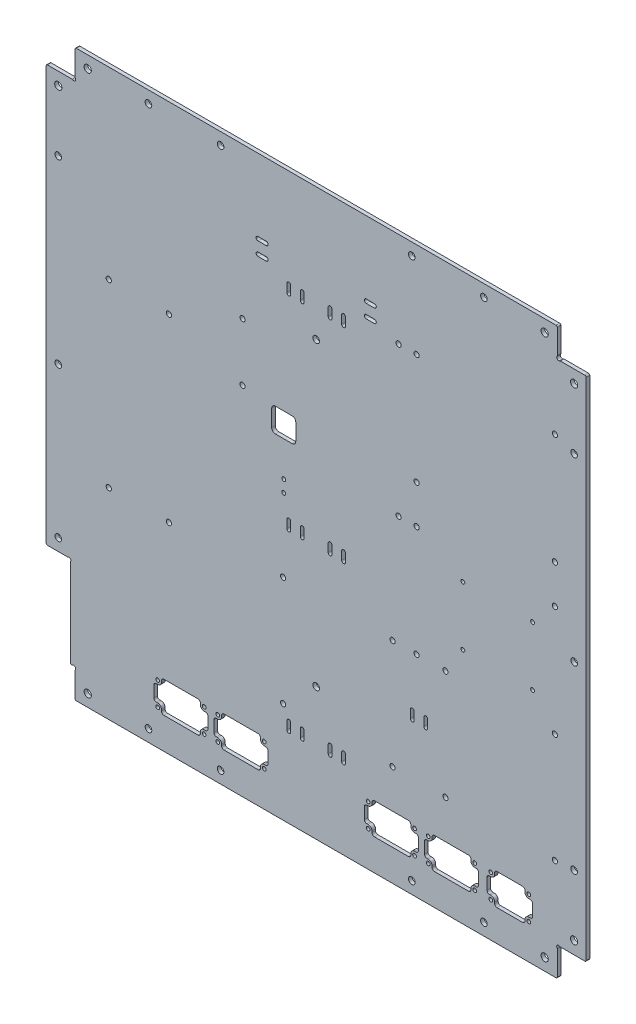
SolidWorks part; units mm, degrees
material "Acrylic (Medium-high impact)"
ref_plane "Front" through (0, 0, 0) normal (0, 0, 1) x (1, 0, 0)
ref_plane "Top" through (0, 0, 0) normal (0, 1, 0) x (1, 0, 0)
ref_plane "Right" through (0, 0, 0) normal (1, 0, 0) x (0, 0, -1)
sketch "Sketch2" plane through (0, 0, 0) normal (0, 0, 1) x (1, 0, 0)
  line L1 (0, 0) -> (449, 0)
  line L2 (0, 0) -> (0, 470)
  line L3 (0, 470) -> (449, 470)
  line L4 (449, 0) -> (449, 470)
  dimension "D1" = 449
  dimension "D2" = 470
extrude "Boss-Extrude1" add sketch "Sketch2" along normal blind 3
sketch "Sketch23" plane through (0, 0, 0) normal (0, 0, -1) x (-1, 0, 0)
  line L0 (-449, 470) -> (0, 470) construction
  line L1 (-449, 470) -> (-429, 470)
  line L2 (-449, 470) -> (-449, 450)
  line L3 (-449, 450) -> (-429, 450)
  line L4 (-429, 470) -> (-429, 450)
  line L5 (0, 470) -> (-20, 470)
  line L6 (0, 470) -> (0, 450)
  line L7 (0, 450) -> (-20, 450)
  line L8 (-20, 470) -> (-20, 450)
  line L9 (0, 470) -> (0, 0) construction
  line L11 (0, 0) -> (-20, 0)
  line L12 (0, 0) -> (0, 20)
  line L13 (0, 20) -> (-20, 20)
  line L14 (-20, 0) -> (-20, 20)
  line L15 (-449, 0) -> (-429, 0)
  line L16 (-449, 0) -> (-449, 20)
  line L17 (-449, 20) -> (-429, 20)
  line L18 (-429, 0) -> (-429, 20)
  dimension "D1" = 20
  dimension "D2" = 20
hole_wizard "M5 Clearance Hole1" positions "Sketch4" profile "Sketch5" hole size "M5" standard "ANSI Metric" end condition up to next
sketch "Sketch4" plane through (0, 0, 0) normal (0, 0, -1) x (-1, 0, 0)
  line L0 (-224.5, 470) -> (-224.5, 0) construction
  line L1 (-449, 470) -> (0, 470) construction
  line L2 (0, 0) -> (-449, 0) construction
  line L3 (-429, 460) -> (-364, 460) construction
  line L6 (-364, 460) -> (-85, 460) construction
  line L7 (-85, 460) -> (-20, 460) construction
  line L9 (-449, 235) -> (0, 235) construction
  line L10 (-449, 0) -> (-449, 470) construction
  line L12 (0, 470) -> (0, 0) construction
  line L13 (-439, 450) -> (-439, 20) construction
  line L18 (-10, 450) -> (-10, 20) construction
  line L21 (-429, 10) -> (-20, 10) construction
  line L31 (-20, 470) -> (-20, 450) construction
  line L32 (-429, 470) -> (-429, 450) construction
  line L33 (-449, 450) -> (-429, 450) construction
  line L34 (-449, 20) -> (-429, 20) construction
  line L35 (-429, 0) -> (-429, 20) construction
  line L36 (0, 450) -> (-20, 450) construction
  line L37 (0, 20) -> (-20, 20) construction
  line L38 (-20, 0) -> (-20, 20) construction
  point P13 (-224.5, 360)
  point P17 (-224.5, 110)
  point P24 (-364, 460)
  point P29 (-85, 460)
  point P54 (-304, 460)
  point P56 (-145, 460)
  point P59 (-85, 10)
  point P60 (-145, 10)
  point P61 (-304, 10)
  point P62 (-364, 10)
  point P83 (-439, 385)
  point P85 (-439, 85)
  point P92 (-10, 110)
  point P93 (-10, 385)
  point P97 (-439, 235)
  point P103 (-10, 235)
  dimension "D5" = 65
  dimension "D8" = 65
  dimension "D3" = 100
  dimension "D2" = 100
  dimension "D1" = 60
  dimension "D4" = 60
  dimension "D6" = 90
  dimension "D9" = 65
sketch "Sketch5" plane through (10, 235, 0) normal (1, 0, 0) x (0, 1, 0)
  line L0 (0, 0) -> (0, 3)
  line L1 (0, 3) -> (2.75, 3)
  line L2 (2.75, 3) -> (2.75, 0)
  line L5 (2.75, 0) -> (0, 0)
  line L11 (0, -6.35) -> (0, 107.95) construction
  dimension "Thru Hole Dia." = 5.5
  dimension "Thru Hole Depth" = 3
sketch "Sketch10" plane through (0, 0, 0) normal (0, 0, -1) x (-1, 0, 0)
  line L0 (-20, 20) -> (-429, 20) construction
  line L1 (-134.5, 26) -> (-89.5, 26) construction
  line L2 (-134.5, 26) -> (-134.5, 52) construction
  line L3 (-134.5, 52) -> (-89.5, 52) construction
  line L4 (-89.5, 26) -> (-89.5, 52) construction
  line L7 (-224.5, 20) -> (-224.5, 145.1565) construction
  line L8 (-128.15, 52) -> (-128.15, 45.65)
  line L15 (-139.5, 52) -> (-184.5, 52) construction
  line L16 (-139.5, 52) -> (-139.5, 26) construction
  line L17 (-139.5, 26) -> (-184.5, 26) construction
  line L18 (-184.5, 52) -> (-184.5, 26) construction
  line L22 (-128.15, 45.65) -> (-134.5, 45.65)
  line L23 (-134.5, 45.65) -> (-134.5, 32.35)
  line L24 (-134.5, 32.35) -> (-128.15, 32.35)
  line L25 (-128.15, 32.35) -> (-128.15, 26)
  line L26 (-128.15, 26) -> (-95.85, 26)
  line L27 (-95.85, 26) -> (-95.85, 32.35)
  line L28 (-95.85, 32.35) -> (-89.5, 32.35)
  line L29 (-89.5, 32.35) -> (-89.5, 45.65)
  line L30 (-89.5, 45.65) -> (-95.85, 45.65)
  line L31 (-95.85, 45.65) -> (-95.85, 52)
  line L32 (-95.85, 52) -> (-128.15, 52)
  line L33 (-178.15, 52) -> (-178.15, 45.65)
  line L34 (-178.15, 45.65) -> (-184.5, 45.65)
  line L35 (-184.5, 45.65) -> (-184.5, 32.35)
  line L36 (-184.5, 32.35) -> (-178.15, 32.35)
  line L37 (-178.15, 32.35) -> (-178.15, 26)
  line L38 (-178.15, 26) -> (-145.85, 26)
  line L39 (-145.85, 26) -> (-145.85, 32.35)
  line L40 (-145.85, 32.35) -> (-139.5, 32.35)
  line L41 (-139.5, 32.35) -> (-139.5, 45.65)
  line L42 (-139.5, 45.65) -> (-145.85, 45.65)
  line L43 (-145.85, 45.65) -> (-145.85, 52)
  line L44 (-145.85, 52) -> (-178.15, 52)
  line L45 (-264.5, 52) -> (-264.5, 26) construction
  line L46 (-309.5, 26) -> (-264.5, 26) construction
  line L47 (-309.5, 52) -> (-309.5, 26) construction
  line L48 (-309.5, 52) -> (-264.5, 52) construction
  line L49 (-359.5, 26) -> (-359.5, 52) construction
  line L50 (-314.5, 52) -> (-359.5, 52) construction
  line L51 (-314.5, 26) -> (-314.5, 52) construction
  line L52 (-314.5, 26) -> (-359.5, 26) construction
  line L53 (-303.15, 52) -> (-270.85, 52)
  line L54 (-303.15, 45.65) -> (-303.15, 52)
  line L55 (-309.5, 45.65) -> (-303.15, 45.65)
  line L56 (-309.5, 32.35) -> (-309.5, 45.65)
  line L57 (-303.15, 32.35) -> (-309.5, 32.35)
  line L58 (-303.15, 26) -> (-303.15, 32.35)
  line L59 (-270.85, 26) -> (-303.15, 26)
  line L60 (-270.85, 32.35) -> (-270.85, 26)
  line L61 (-264.5, 32.35) -> (-270.85, 32.35)
  line L62 (-264.5, 45.65) -> (-264.5, 32.35)
  line L63 (-270.85, 45.65) -> (-264.5, 45.65)
  line L64 (-270.85, 52) -> (-270.85, 45.65)
  line L65 (-353.15, 52) -> (-320.85, 52)
  line L66 (-353.15, 45.65) -> (-353.15, 52)
  line L67 (-359.5, 45.65) -> (-353.15, 45.65)
  line L68 (-359.5, 32.35) -> (-359.5, 45.65)
  line L69 (-353.15, 32.35) -> (-359.5, 32.35)
  line L70 (-353.15, 26) -> (-353.15, 32.35)
  line L71 (-320.85, 26) -> (-353.15, 26)
  line L72 (-320.85, 32.35) -> (-320.85, 26)
  line L73 (-314.5, 32.35) -> (-320.85, 32.35)
  line L74 (-314.5, 45.65) -> (-314.5, 32.35)
  line L75 (-320.85, 45.65) -> (-314.5, 45.65)
  line L76 (-320.85, 52) -> (-320.85, 45.65)
  line L77 (0, 0) -> (-449, 0) construction
  dimension "D1" = 6.35
  dimension "D2" = 45
  dimension "D3" = 40
  dimension "D4" = 26
  dimension "D5" = 5
  dimension "D6" = 26
extrude "extruder panel cutouts" cut sketch "Sketch10" against normal through all
sketch "Sketch16" plane through (0, 0, 0) normal (0, 0, -1) x (-1, 0, 0)
  line L0 (-353.15, 26) -> (-320.85, 26) construction
  line L1 (-366.5, 26) -> (-404.5, 26) construction
  line L2 (-366.5, 26) -> (-366.5, 52) construction
  line L3 (-366.5, 52) -> (-404.5, 52) construction
  line L4 (-404.5, 26) -> (-404.5, 52) construction
  line L6 (-398.15, 52) -> (-398.15, 45.65)
  line L7 (-398.15, 45.65) -> (-404.5, 45.65)
  line L8 (-404.5, 45.65) -> (-404.5, 32.35)
  line L9 (-404.5, 32.35) -> (-398.15, 32.35)
  line L10 (-398.15, 32.35) -> (-398.15, 26)
  line L11 (-398.15, 26) -> (-372.85, 26)
  line L12 (-372.85, 26) -> (-372.85, 32.35)
  line L13 (-372.85, 32.35) -> (-366.5, 32.35)
  line L14 (-366.5, 32.35) -> (-366.5, 45.65)
  line L15 (-366.5, 45.65) -> (-372.85, 45.65)
  line L16 (-372.85, 45.65) -> (-372.85, 52)
  line L17 (-372.85, 52) -> (-398.15, 52)
  line L18 (-449, 0) -> (-449, 470) construction
  dimension "D1" = 26
  dimension "D2" = 38
  dimension "D3" = 44.5
  dimension "D4" = 6.35
extrude "z_motor_panel_cutout" cut sketch "Sketch16" against normal blind 10
fillet "Fillet1" radius 3.175 20 edges at (95.85, 45.65, 1.5) (95.85, 32.35, 1.5) (128.15, 32.35, 1.5) (128.15, 45.65, 1.5) (178.15, 32.35, 1.5) (178.15, 45.65, 1.5) (145.85, 32.35, 1.5) (145.85, 45.65, 1.5) (353.15, 45.65, 1.5) (353.15, 32.35, 1.5) (320.85, 32.35, 1.5) (320.85, 45.65, 1.5) (303.15, 32.35, 1.5) (303.15, 45.65, 1.5) (270.85, 32.35, 1.5) (270.85, 45.65, 1.5) (398.15, 32.35, 1.5) (372.85, 45.65, 1.5) (372.85, 32.35, 1.5) (398.15, 45.65, 1.5)
sketch "Sketch17" plane through (0, 0, 0) normal (0, 0, -1) x (-1, 0, 0)
  circle A0 centre (-401.325, 48.825) radius 1.55
  circle A1 centre (-369.675, 48.825) radius 1.55
  circle A2 centre (-369.675, 29.175) radius 1.55
  circle A3 centre (-401.325, 29.175) radius 1.55
  circle A4 centre (-356.325, 48.825) radius 1.55
  circle A5 centre (-317.675, 48.825) radius 1.55
  circle A6 centre (-317.675, 29.175) radius 1.55
  circle A7 centre (-356.325, 29.175) radius 1.55
  circle A8 centre (-306.325, 48.825) radius 1.55
  circle A9 centre (-267.675, 48.825) radius 1.55
  circle A10 centre (-267.675, 29.175) radius 1.55
  circle A11 centre (-306.325, 29.175) radius 1.55
  circle A12 centre (-181.325, 48.825) radius 1.55
  circle A13 centre (-142.675, 48.825) radius 1.55
  circle A14 centre (-142.675, 29.175) radius 1.55
  circle A15 centre (-181.325, 29.175) radius 1.55
  circle A16 centre (-131.325, 48.825) radius 1.55
  circle A17 centre (-92.675, 48.825) radius 1.55
  circle A18 centre (-92.675, 29.175) radius 1.55
  circle A19 centre (-131.325, 29.175) radius 1.55
  dimension "D1" = 3.1
extrude "Cut-Extrude3" cut sketch "Sketch17" against normal through all
sketch "Sketch7" plane through (0, 0, 0) normal (0, 0, -1) x (-1, 0, 0)
  line L0 (-449, 0) -> (-449, 470) construction
  line L1 (-423, 299) -> (-308, 299) construction
  line L2 (-423, 299) -> (-423, 391) construction
  line L3 (-423, 391) -> (-308, 391) construction
  line L4 (-308, 299) -> (-308, 391) construction
  line L5 (-423, 299) -> (-308, 391) construction
  line L6 (-423, 391) -> (-308, 299) construction
  line L7 (-304, 295) -> (-427, 295) construction
  line L8 (-304, 295) -> (-304, 395) construction
  line L9 (-304, 395) -> (-427, 395) construction
  line L10 (-427, 295) -> (-427, 395) construction
  line L11 (-304, 295) -> (-427, 395) construction
  line L12 (-304, 395) -> (-427, 295) construction
  line L14 (-423, 175) -> (-308, 175) construction
  line L15 (-423, 175) -> (-423, 267) construction
  line L16 (-423, 267) -> (-308, 267) construction
  line L17 (-308, 175) -> (-308, 267) construction
  line L18 (-423, 175) -> (-308, 267) construction
  line L19 (-423, 267) -> (-308, 175) construction
  line L20 (-304, 171) -> (-427, 171) construction
  line L21 (-304, 171) -> (-304, 271) construction
  line L22 (-304, 271) -> (-427, 271) construction
  line L23 (-427, 171) -> (-427, 271) construction
  line L24 (-304, 171) -> (-427, 271) construction
  line L25 (-304, 271) -> (-427, 171) construction
  circle A0 centre (-423, 391) radius 2.15
  circle A1 centre (-308, 391) radius 2.15
  circle A2 centre (-308, 299) radius 2.15
  circle A3 centre (-423, 299) radius 2.15
  circle A4 centre (-423, 267) radius 2.15
  circle A5 centre (-308, 267) radius 2.15
  circle A6 centre (-308, 175) radius 2.15
  circle A7 centre (-423, 175) radius 2.15
  point P0 (-365.5, 345)
  point P6 (-365.5, 345)
  point P19 (-365.5, 221)
  point P25 (-365.5, 221)
  dimension "D5" = 4.3
  dimension "D12" = 4.3
  dimension "D1" = 115
  dimension "D2" = 92
  dimension "D3" = 123
  dimension "D4" = 100
  dimension "D6" = 22
  dimension "D7" = 55
  dimension "D8" = 115
  dimension "D9" = 92
  dimension "D10" = 123
  dimension "D11" = 100
  dimension "D13" = 24
extrude "Duet2 mounting holes" cut sketch "Sketch7" against normal through all
sketch "Sketch9" plane through (0, 0, 0) normal (0, 0, -1) x (-1, 0, 0)
  line L0 (0, 470) -> (0, 0) construction
  line L1 (-102, 167) -> (-52, 167) construction
  line L2 (-102, 167) -> (-102, 317) construction
  line L3 (-102, 317) -> (-52, 317) construction
  line L4 (-52, 167) -> (-52, 317) construction
  line L5 (-102, 167) -> (-52, 317) construction
  line L6 (-102, 317) -> (-52, 167) construction
  line L8 (0, 0) -> (-449, 0) construction
  line L9 (-20, 135) -> (-134, 135) construction
  line L10 (-20, 135) -> (-20, 349) construction
  line L11 (-20, 349) -> (-134, 349) construction
  line L12 (-134, 135) -> (-134, 349) construction
  line L13 (-20, 135) -> (-134, 349) construction
  line L14 (-20, 349) -> (-134, 135) construction
  circle A0 centre (-52, 317) radius 2.2
  circle A1 centre (-102, 317) radius 2.2
  circle A2 centre (-52, 167) radius 2.2
  circle A3 centre (-102, 167) radius 2.2
  point P0 (-77, 242)
  point P11 (-77, 242)
  point P21 (-77, 317)
  dimension "D1" = 50
  dimension "D3" = 4.4
  dimension "D2" = 114
  dimension "D4" = 32
  dimension "D5" = 150
  dimension "D6" = 20
  dimension "D7" = 135
extrude "psu mounting holes" cut sketch "Sketch9" against normal through all
sketch "Sketch11" plane through (0, 0, 0) normal (0, 0, -1) x (-1, 0, 0)
  line L0 (-224.5, 0) -> (-224.5, 150.8562) construction
  line L1 (0, 0) -> (-449, 0) construction
  line L2 (-163.25, 296.4) -> (-163.25, 344.4) construction
  circle A0 centre (-163.25, 344.4) radius 2.15
  circle A1 centre (-163.25, 296.4) radius 2.15
  dimension "D1" = 48
  dimension "D2" = 4.3
  dimension "D3" = 296.4
  dimension "D4" = 61.25
extrude "ssr holes" cut sketch "Sketch11" against normal through all
sketch "Sketch18" plane through (0, 0, 0) normal (0, 0, -1) x (-1, 0, 0)
  line L0 (-423, 267) -> (-293, 267) construction
  line L1 (-423, 391) -> (-293, 391) construction
  line L2 (-428, 396) -> (-288, 396) construction
  line L3 (-423, 391) -> (-293, 391) construction
  line L4 (-423, 391) -> (-423, 267) construction
  line L5 (-423, 267) -> (-293, 267) construction
  line L6 (-293, 391) -> (-293, 267) construction
  line L7 (-288, 396) -> (-288, 262) construction
  line L8 (-428, 262) -> (-288, 262) construction
  line L9 (-428, 396) -> (-428, 262) construction
  line L10 (-404.5, 246.5) -> (-346.5, 246.5) construction
  line L11 (-428, 250) -> (-343, 250) construction
  line L12 (-428, 250) -> (-428, 194) construction
  line L13 (-428, 194) -> (-343, 194) construction
  line L14 (-343, 250) -> (-343, 194) construction
  line L15 (-346.5, 246.5) -> (-346.5, 197.5) construction
  line L16 (-346.5, 197.5) -> (-404.5, 197.5) construction
  line L17 (-404.5, 197.5) -> (-404.5, 246.5) construction
  line L18 (-423, 84) -> (-423, 175) construction
  line L19 (-427.5, 79.5) -> (-327.5, 79.5) construction
  line L20 (-427.5, 79.5) -> (-427.5, 179.5) construction
  line L21 (-427.5, 179.5) -> (-327.5, 179.5) construction
  line L22 (-327.5, 79.5) -> (-327.5, 179.5) construction
  line L23 (-423, 175) -> (-332, 175) construction
  line L24 (-332, 84) -> (-332, 175) construction
  line L25 (-423, 84) -> (-332, 84) construction
  line L26 (-192.5, 179.5) -> (-292.5, 179.5) construction
  line L27 (-197, 175) -> (-288, 175) construction
  line L28 (-197, 175) -> (-197, 84) construction
  line L29 (-197, 84) -> (-288, 84) construction
  line L30 (-288, 175) -> (-288, 84) construction
  line L31 (-292.5, 179.5) -> (-292.5, 79.5) construction
  line L32 (-192.5, 79.5) -> (-292.5, 79.5) construction
  line L33 (-192.5, 179.5) -> (-192.5, 79.5) construction
  circle A0 centre (-293, 391) radius 2.15
  circle A1 centre (-423, 391) radius 2.15 construction
  circle A2 centre (-293, 267) radius 2.15
  circle A3 centre (-404.5, 246.5) radius 1.6
  circle A4 centre (-346.5, 246.5) radius 1.6
  circle A5 centre (-346.5, 197.5) radius 1.6
  circle A6 centre (-404.5, 197.5) radius 1.6
  circle A7 centre (-332, 175) radius 2.15
  circle A8 centre (-332, 84) radius 2.15
  circle A9 centre (-423, 84) radius 2.15
  circle A10 centre (-423, 175) radius 2.15 construction
  circle A11 centre (-288, 175) radius 2.15
  circle A12 centre (-288, 84) radius 2.15
  circle A13 centre (-197, 84) radius 2.15
  circle A14 centre (-163.25, 344.4) radius 2.15 construction
  circle A15 centre (-197, 175) radius 2.15
  dimension "D2" = 4.3
  dimension "D11" = 3.2
  dimension "D1" = 130
  dimension "D3" = 124
  dimension "D5" = 85
  dimension "D6" = 56
  dimension "D8" = 3.5
  dimension "D9" = 3.5
  dimension "D10" = 58
  dimension "D12" = 12
  dimension "D7" = 3.5
  dimension "D14" = 100
  dimension "D16" = 91
  dimension "D13" = 14.5
  dimension "D17" = 91
  dimension "D19" = 35
  dimension "D4" = 5
  dimension "D15" = 4.5
  dimension "D18" = 4.5
extrude "Duet3, Expanders, and Raspi Holes" cut sketch "Sketch18" against normal through all
sketch "Sketch12" plane through (0, 0, 0) normal (0, 0, -1) x (-1, 0, 0)
  line L0 (-414.5, 460) -> (-429, 460) construction
  line L2 (-20, 460) -> (-34.5, 460) construction
  line L4 (-439, 450) -> (-439, 435.5) construction
  line L6 (-439, 20) -> (-439, 34.5) construction
  line L8 (-429, 10) -> (-414.5, 10) construction
  line L10 (-20, 10) -> (-34.5, 10) construction
  line L12 (-10, 20) -> (-10, 34.5) construction
  line L14 (-10, 450) -> (-10, 435.5) construction
  line L19 (-429, 0) -> (-429, 20) construction
  circle A0 centre (-414.5, 460) radius 3
  circle A1 centre (-34.5, 460) radius 3
  circle A2 centre (-439, 435.5) radius 3
  circle A3 centre (-439, 34.5) radius 3
  circle A4 centre (-414.5, 10) radius 3
  circle A5 centre (-34.5, 10) radius 3
  circle A6 centre (-10, 34.5) radius 3
  circle A7 centre (-10, 435.5) radius 3
  dimension "D1" = 14.5
  dimension "D2" = 6
extrude "inside corner bracket screw clearance holes" cut sketch "Sketch12" against normal through all
sketch "Sketch6" plane through (0, 0, 0) normal (0, 0, -1) x (-1, 0, 0)
  line L0 (-224.5, 470) -> (-224.5, 0) construction
  line L1 (-449, 470) -> (0, 470) construction
  line L2 (0, 0) -> (-449, 0) construction
  line L3 (-234.5, 470) -> (-234.5, 0) construction
  line L4 (-429, 450) -> (-20, 450) construction
  line L5 (-245.675, 220) -> (-245.675, 210)
  line L6 (-234.5, 390) -> (-237.675, 390)
  line L7 (-234.5, 390) -> (-234.5, 380)
  line L8 (-234.5, 380) -> (-237.675, 380)
  line L9 (-237.675, 390) -> (-237.675, 380)
  line L10 (-245.675, 390) -> (-248.85, 390)
  line L11 (-245.675, 390) -> (-245.675, 380)
  line L12 (-245.675, 380) -> (-248.85, 380)
  line L13 (-248.85, 390) -> (-248.85, 380)
  line L14 (-245.675, 220) -> (-248.85, 220)
  line L15 (-248.85, 220) -> (-248.85, 210)
  line L16 (-245.675, 210) -> (-248.85, 210)
  line L17 (-234.5, 220) -> (-234.5, 210)
  line L18 (-234.5, 220) -> (-237.675, 220)
  line L19 (-237.675, 220) -> (-237.675, 210)
  line L20 (-234.5, 210) -> (-237.675, 210)
  line L69 (-214.5, 210) -> (-211.325, 210)
  line L70 (-211.325, 220) -> (-211.325, 210)
  line L71 (-214.5, 220) -> (-211.325, 220)
  line L72 (-214.5, 220) -> (-214.5, 210)
  line L73 (-203.325, 210) -> (-200.15, 210)
  line L74 (-200.15, 220) -> (-200.15, 210)
  line L75 (-203.325, 220) -> (-200.15, 220)
  line L76 (-200.15, 390) -> (-200.15, 380)
  line L77 (-203.325, 380) -> (-200.15, 380)
  line L78 (-203.325, 390) -> (-203.325, 380)
  line L79 (-203.325, 390) -> (-200.15, 390)
  line L80 (-211.325, 390) -> (-211.325, 380)
  line L81 (-214.5, 380) -> (-211.325, 380)
  line L82 (-214.5, 390) -> (-214.5, 380)
  line L83 (-214.5, 390) -> (-211.325, 390)
  line L84 (-203.325, 220) -> (-203.325, 210)
  line L85 (-245.675, 75) -> (-245.675, 65)
  line L86 (-245.675, 65) -> (-248.85, 65)
  line L87 (-248.85, 75) -> (-248.85, 65)
  line L88 (-245.675, 75) -> (-248.85, 75)
  line L89 (-234.5, 75) -> (-234.5, 65)
  line L90 (-234.5, 65) -> (-237.675, 65)
  line L91 (-237.675, 75) -> (-237.675, 65)
  line L92 (-234.5, 75) -> (-237.675, 75)
  line L93 (-214.5, 65) -> (-211.325, 65)
  line L98 (-211.325, 75) -> (-211.325, 65)
  line L99 (-214.5, 75) -> (-211.325, 75)
  line L104 (-214.5, 75) -> (-214.5, 65)
  line L105 (-174.5, 406.825) -> (-174.5, 410)
  line L106 (-274.5, 395.65) -> (-264.5, 395.65)
  line L107 (-274.5, 395.65) -> (-274.5, 398.825)
  line L108 (-274.5, 398.825) -> (-264.5, 398.825)
  line L109 (-264.5, 395.65) -> (-264.5, 398.825)
  line L110 (-264.5, 406.825) -> (-274.5, 406.825)
  line L111 (-264.5, 406.825) -> (-264.5, 410)
  line L112 (-264.5, 410) -> (-274.5, 410)
  line L113 (-274.5, 406.825) -> (-274.5, 410)
  line L114 (-184.5, 410) -> (-174.5, 410)
  line L115 (-184.5, 406.825) -> (-184.5, 410)
  line L116 (-184.5, 406.825) -> (-174.5, 406.825)
  line L117 (-184.5, 395.65) -> (-184.5, 398.825)
  line L118 (-174.5, 398.825) -> (-184.5, 398.825)
  line L119 (-174.5, 395.65) -> (-174.5, 398.825)
  line L120 (-174.5, 395.65) -> (-184.5, 395.65)
  line L121 (-245.675, 50) -> (-245.675, 40) [skipped]
  line L122 (-245.675, 50) -> (-248.85, 50) [skipped]
  line L123 (-248.85, 50) -> (-248.85, 40) [skipped]
  line L124 (-245.675, 40) -> (-248.85, 40) [skipped]
  line L125 (-234.5, 50) -> (-234.5, 40) [skipped]
  line L126 (-234.5, 50) -> (-237.675, 50) [skipped]
  line L127 (-237.675, 50) -> (-237.675, 40) [skipped]
  line L128 (-234.5, 40) -> (-237.675, 40) [skipped]
  line L129 (-203.325, 65) -> (-200.15, 65)
  line L130 (-200.15, 75) -> (-200.15, 65)
  line L131 (-203.325, 75) -> (-200.15, 75)
  line L132 (-203.325, 75) -> (-203.325, 65)
  line L133 (-315.5875, 129.5) -> (-327.5, 129.5) construction
  line L136 (-327.5, 79.5) -> (-327.5, 179.5) construction
  line L137 (-317.175, 124.5) -> (-314, 124.5)
  line L138 (-317.175, 124.5) -> (-317.175, 134.5)
  line L139 (-317.175, 134.5) -> (-314, 134.5)
  line L140 (-314, 124.5) -> (-314, 134.5)
  line L141 (-317.175, 124.5) -> (-314, 134.5) construction
  line L142 (-317.175, 134.5) -> (-314, 124.5) construction
  line L143 (-306, 124.5) -> (-302.825, 124.5)
  line L144 (-306, 124.5) -> (-306, 134.5)
  line L145 (-306, 134.5) -> (-302.825, 134.5)
  line L146 (-302.825, 124.5) -> (-302.825, 134.5)
  line L147 (-306, 124.5) -> (-302.825, 134.5) construction
  line L148 (-306, 134.5) -> (-302.825, 124.5) construction
  line L149 (-315.5875, 129.5) -> (-304.4125, 129.5) construction
  line L150 (-304.4125, 129.5) -> (-292.5, 129.5) construction
  line L151 (-292.5, 179.5) -> (-292.5, 79.5) construction
  point P82 (-315.5875, 129.5)
  point P87 (-304.4125, 129.5)
  dimension "D1" = 10
  dimension "D3" = 3.175
  dimension "D4" = 8
  dimension "D6" = 60
  dimension "D11" = 8
  dimension "D12" = 60
  dimension "D13" = 40
  dimension "D7" = 170
  dimension "D9" = 145
  dimension "D10" = 8
extrude "main wiring tie-downs" cut sketch "Sketch6" against normal through all
sketch "Sketch13" plane through (0, 0, 0) normal (0, 0, -1) x (-1, 0, 0)
  line L1 (-449, 0) -> (-425, 0)
  line L2 (-449, 0) -> (-449, 24)
  line L3 (-449, 24) -> (-425, 24)
  line L4 (-425, 0) -> (-425, 24)
  line L5 (0, 0) -> (-24, 0)
  line L6 (0, 0) -> (0, 24)
  line L7 (0, 24) -> (-24, 24)
  line L8 (-24, 0) -> (-24, 24)
  line L12 (-429, 0) -> (-429, 20) construction
  line L15 (-449, 470) -> (-425, 470)
  line L16 (-449, 470) -> (-449, 446)
  line L17 (-449, 446) -> (-425, 446)
  line L18 (-425, 470) -> (-425, 446)
  line L19 (0, 470) -> (-24, 470)
  line L20 (0, 470) -> (0, 446)
  line L21 (0, 446) -> (-24, 446)
  line L22 (-24, 470) -> (-24, 446)
  line L24 (-449, 20) -> (-429, 20) construction
  line L25 (0, 20) -> (-20, 20) construction
  line L26 (-449, 450) -> (-429, 450) construction
  line L27 (0, 450) -> (-20, 450) construction
  dimension "3" = 4
  dimension "D1" = 4
  dimension "D2" = 4
  dimension "D3" = 4
  dimension "D4" = 4
extrude "Cut-Extrude1" cut sketch "Sketch13" against normal through all
fillet "Fillet3" radius 2 40 edges at (89.5, 45.65, 1.5) (95.85, 52, 1.5) (95.85, 26, 1.5) (89.5, 32.35, 1.5) (134.5, 32.35, 1.5) (128.15, 26, 1.5) (134.5, 45.65, 1.5) (128.15, 52, 1.5) (145.85, 52, 1.5) (139.5, 45.65, 1.5) (184.5, 45.65, 1.5) (178.15, 52, 1.5) (184.5, 32.35, 1.5) (178.15, 26, 1.5) (139.5, 32.35, 1.5) (145.85, 26, 1.5) (264.5, 32.35, 1.5) (270.85, 26, 1.5) (264.5, 45.65, 1.5) (270.85, 52, 1.5) (303.15, 52, 1.5) (309.5, 45.65, 1.5) (303.15, 26, 1.5) (309.5, 32.35, 1.5) (320.85, 52, 1.5) (314.5, 45.65, 1.5) (353.15, 52, 1.5) (359.5, 45.65, 1.5) (359.5, 32.35, 1.5) (353.15, 26, 1.5) (314.5, 32.35, 1.5) (320.85, 26, 1.5) (372.85, 26, 1.5) (398.15, 26, 1.5) (404.5, 32.35, 1.5) (366.5, 32.35, 1.5) (366.5, 45.65, 1.5) (372.85, 52, 1.5) (404.5, 45.65, 1.5) (398.15, 52, 1.5)
fillet "Fillet4" radius 1.5875 72 edges at (200.15, 210, 1.5) (211.325, 210, 1.5) (234.5, 210, 1.5) (245.675, 210, 1.5) (248.85, 210, 1.5) (237.675, 210, 1.5) (214.5, 210, 1.5) (203.325, 210, 1.5) (203.325, 220, 1.5) (214.5, 220, 1.5) (237.675, 220, 1.5) (248.85, 220, 1.5) (245.675, 220, 1.5) (234.5, 220, 1.5) (211.325, 220, 1.5) (200.15, 220, 1.5) (264.5, 398.825, 1.5) (264.5, 410, 1.5) (274.5, 406.825, 1.5) (274.5, 395.65, 1.5) (274.5, 398.825, 1.5) (274.5, 410, 1.5) (264.5, 395.65, 1.5) (264.5, 406.825, 1.5) (245.675, 380, 1.5) (234.5, 380, 1.5) (237.675, 380, 1.5) (248.85, 380, 1.5) (234.5, 390, 1.5) (245.675, 390, 1.5) (237.675, 390, 1.5) (248.85, 390, 1.5) (214.5, 390, 1.5) (211.325, 390, 1.5) (211.325, 380, 1.5) (214.5, 380, 1.5) (203.325, 380, 1.5) (203.325, 390, 1.5) (200.15, 390, 1.5) (200.15, 380, 1.5) (174.5, 395.65, 1.5) (174.5, 398.825, 1.5) (184.5, 398.825, 1.5) (184.5, 395.65, 1.5) (184.5, 406.825, 1.5) (174.5, 406.825, 1.5) (174.5, 410, 1.5) (184.5, 410, 1.5) (214.5, 65, 1.5) (211.325, 65, 1.5) (214.5, 75, 1.5) (211.325, 75, 1.5) (200.15, 75, 1.5) (203.325, 75, 1.5) (203.325, 65, 1.5) (200.15, 65, 1.5) (245.675, 65, 1.5) (248.85, 65, 1.5) (248.85, 75, 1.5) (245.675, 75, 1.5) (237.675, 65, 1.5) (234.5, 65, 1.5) (237.675, 75, 1.5) (234.5, 75, 1.5) (317.175, 134.5, 1.5) (314, 134.5, 1.5) (306, 134.5, 1.5) (302.825, 134.5, 1.5) (317.175, 124.5, 1.5) (314, 124.5, 1.5) (306, 124.5, 1.5) (302.825, 124.5, 1.5)
sketch "Sketch19" plane through (0, 0, 0) normal (0, 0, -1) x (-1, 0, 0)
  line L0 (0, 0) -> (-20, 0) construction
  line L1 (-20, 100) -> (0, 100)
  line L2 (-20, 100) -> (-20, 0)
  line L3 (-20, 0) -> (0, 0)
  line L4 (0, 100) -> (0, 0)
  line L6 (0, 446) -> (0, 24) construction
  dimension "D3" = 100
extrude "power inlet socket cutout" cut sketch "Sketch19" against normal through all
sketch "Sketch20" plane through (0, 0, 0) normal (0, 0, -1) x (-1, 0, 0)
  line L1 (-187.5, 295) -> (-207.5, 295)
  line L2 (-187.5, 295) -> (-187.5, 275)
  line L3 (-187.5, 275) -> (-207.5, 275)
  line L4 (-207.5, 295) -> (-207.5, 275)
  line L5 (-197.5, 275) -> (-197.5, 295) construction
  line L6 (-224.5, 470) -> (-224.5, 0) construction
  line L7 (-449, 235) -> (0, 235) construction
  dimension "D1" = 27
  dimension "D2" = 20
  dimension "D3" = 40
  dimension "D4" = 20
extrude "Cut-Extrude5" cut sketch "Sketch20" against normal through all
fillet "Fillet6" radius 3 4 edges at (187.5, 275, 1.5) (187.5, 295, 1.5) (207.5, 295, 1.5) (207.5, 275, 1.5)
sketch "Sketch22" plane through (0, 0, 0) normal (0, 0, -1) x (-1, 0, 0)
  line L0 (-197.5, 246) -> (-197.5, 236) construction
  line L1 (-204.5, 275) -> (-190.5, 275) construction
  line L2 (-197.5, 246) -> (-197.5, 275) construction
  circle A0 centre (-197.5, 246) radius 1.6
  circle A1 centre (-197.5, 236) radius 1.6
  dimension "D1" = 3.2
  dimension "D3" = 29
  dimension "D2" = 10
extrude "Cable Chain Attachment Points" cut sketch "Sketch22" against normal through all
fillet "Fillet7" radius 1 9 edges at (449, 24, 1.5) (425, 0, 1.5) (24, 0, 1.5) (20, 24, 1.5) (0, 100, 1.5) (0, 446, 1.5) (24, 470, 1.5) (449, 446, 1.5) (425, 470, 1.5)
other "Move Face1" [suppressed] offset 0.0762 parameters "D1"=0.0762
sketch "Sketch24" plane through (0, 0, 0) normal (0, 0, -1) x (-1, 0, 0)
  line L0 (-24, 446) -> (-22.8757, 447.1243) construction
  line L1 (-1, 100) -> (-20, 100) construction
  line L2 (-18.8775, 98.8775) -> (-20, 100) construction
  line L3 (-24, 24) -> (-22.8757, 22.8757) construction
  line L5 (-21, 24) -> (-24, 24) construction
  line L8 (-24, 446) -> (-1, 446) construction
  line L11 (-425, 446) -> (-426.1243, 447.1243) construction
  line L12 (-448, 446) -> (-425, 446) construction
  line L15 (-425, 24) -> (-426.1243, 22.8757) construction
  line L16 (-425, 24) -> (-448, 24) construction
  circle A10 centre (-18.8775, 98.8775) radius 1.5875
  circle A11 centre (-22.8757, 447.1243) radius 1.59
  circle A12 centre (-426.1243, 447.1243) radius 1.59
  circle A13 centre (-426.1243, 22.8757) radius 1.59
  circle A14 centre (-22.8757, 22.8757) radius 1.59
  dimension "D2" = 45
  dimension "D6" = 1.5875
  dimension "D7" = 45
  dimension "D8" = 1.59
  dimension "D9" = 45
  dimension "D10" = 1.59
  dimension "D11" = 45
  dimension "D12" = 1.59
  dimension "D3" = 45
  dimension "D4" = 1.59
extrude "Cut-Extrude6" cut sketch "Sketch24" against normal through all
fillet "Fillet8" radius 1 10 edges at (20, 97.7549, 1.5) (17.7549, 100, 1.5) (427.2486, 446, 1.5) (425, 448.2486, 1.5) (21.7514, 446, 1.5) (24, 448.2486, 1.5) (427.2486, 24, 1.5) (425, 21.7514, 1.5) (24, 21.7514, 1.5) (21.7514, 24, 1.5)
equation "\"D8@Sketch4\"=\"D5@Sketch4\""
equation "\"D2@Sketch4\"=\"D3@Sketch4\""
equation "\"D11@Sketch6\"=\"D4@Sketch6\""
equation "\"D4@Sketch4\"=\"D1@Sketch4\""
equation "\"D9@Sketch18\"=\"D8@Sketch18\""
equation "\"D18@Sketch18\"=\"D15@Sketch18\""
equation "\"D10@Sketch6\"=\"D4@Sketch6\""
equation "\"D9@Sketch4\"=\"D8@Sketch4\""
equation "\"D1@Sketch13\"=\"3@Sketch13\""
equation "\"D2@Sketch13\"=\"3@Sketch13\""
equation "\"D3@Sketch13\"=\"3@Sketch13\""
equation "\"D4@Sketch13\"=\"3@Sketch13\""
equation "\"cutter_diameter\"=3.175"
equation "\"D3@Sketch6\"=\"cutter_diameter\""
equation "\"D1@Fillet4\"=\"cutter_diameter\"/2"
equation "\"D6@Sketch24\"=\"cutter_diameter\"/2"
